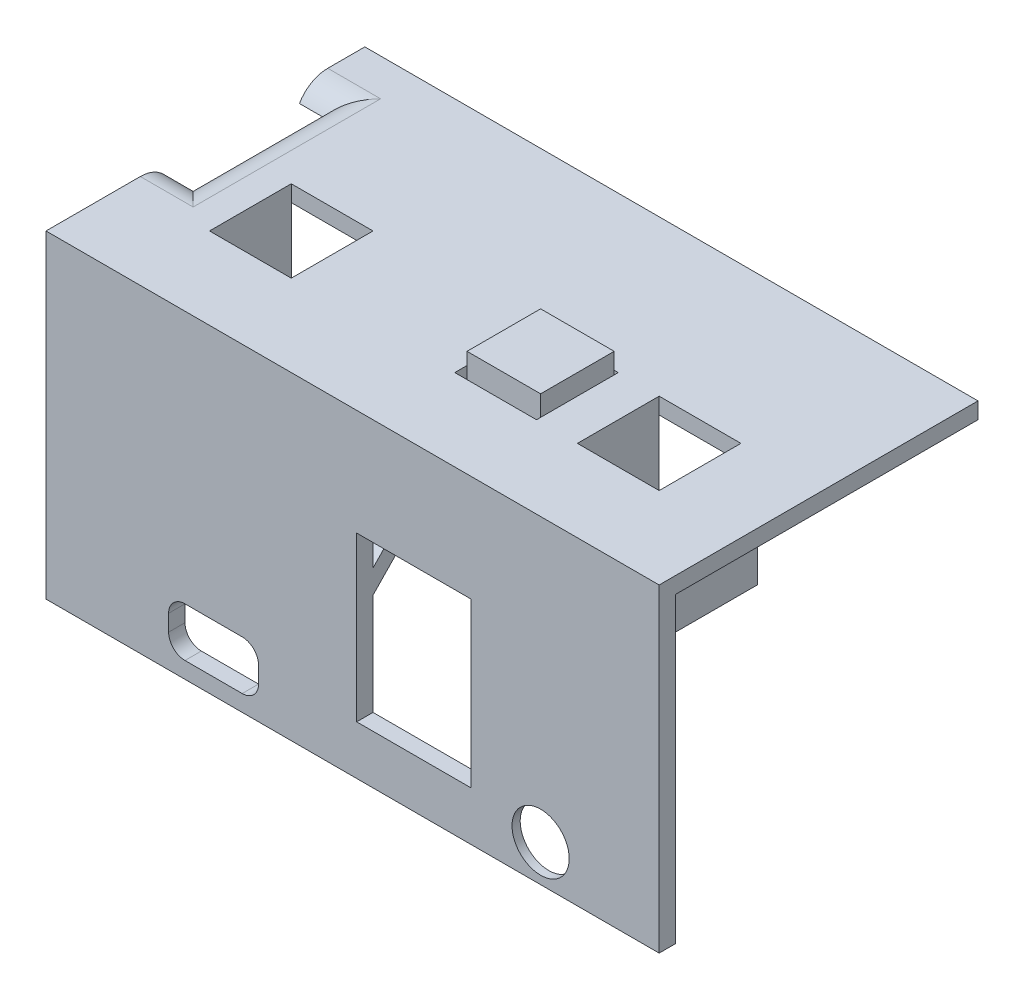
SolidWorks part; units mm, degrees
ref_plane "Front Plane" through (0, 0, 0) normal (0, 0, 1) x (1, 0, 0)
ref_plane "Top Plane" through (0, 0, 0) normal (0, 1, 0) x (1, 0, 0)
ref_plane "Right Plane" through (0, 0, 0) normal (1, 0, 0) x (0, 0, -1)
sketch "Sketch1" plane through (0, 0, 0) normal (0, 0, 1) x (1, 0, 0)
  line L1 (-37.5, 19.5) -> (37.5, 19.5)
  line L2 (-37.5, 19.5) -> (-37.5, -19.5)
  line L3 (-37.5, -19.5) -> (37.5, -19.5)
  line L4 (37.5, 19.5) -> (37.5, -19.5)
  point P4 (37.5, 0)
  point P6 (0, -19.5)
  dimension "D1" = 75
  dimension "D2" = 39
extrude "Boss-Extrude1" add sketch "Sketch1" along normal blind 2
sketch "Sketch2" plane through (0, 0, 0) normal (0, 0, -1) x (-1, 0, 0)
  line L0 (37.5, 19.5) -> (37.5, -19.5) construction
  line L1 (-37.5, 19.5) -> (37.5, 19.5)
  line L2 (-37.5, 19.5) -> (-37.5, 17.5)
  line L3 (-37.5, 17.5) -> (37.5, 17.5)
  line L4 (37.5, 19.5) -> (37.5, 17.5)
  dimension "D1" = 2
extrude "Boss-Extrude2" add sketch "Sketch2" along normal blind 38
sketch "Sketch4" plane through (0, 0, 2) normal (0, 0, 1) x (1, 0, 0)
  line L0 (37.5, -10.5) -> (28.5, -10.5) construction
  line L1 (37.5, -19.5) -> (37.5, 19.5) construction
  line L2 (28.5, -10.5) -> (28.5, -19.5) construction
  line L3 (-37.5, -19.5) -> (37.5, -19.5) construction
  line L4 (23, -19.5) -> (23, -15) construction
  line L5 (-37.5, 19.5) -> (-37.5, -19.5) construction
  line L6 (37.5, 19.5) -> (-37.5, 19.5) construction
  line L7 (-22.5, -11.5) -> (-11.5, -11.5)
  line L8 (-22.5, -11.5) -> (-22.5, -17.5)
  line L9 (-22.5, -17.5) -> (-11.5, -17.5)
  line L10 (-11.5, -11.5) -> (-11.5, -17.5)
  circle A0 centre (23, -15) radius 3.5
  circle A1 centre (23, 4.5) radius 2.25
  dimension "D5" = 7
  dimension "D10" = 4.5
  dimension "D1" = 9
  dimension "D2" = 9
  dimension "D3" = 4.5
  dimension "D4" = 14.5
  dimension "D6" = 15
  dimension "D7" = 49
  dimension "D8" = 2
  dimension "D9" = 6
  dimension "D11" = 15
extrude "Cut-Extrude1" cut sketch "Sketch4" against normal up to surface (2 mm away) up to face at (0, -1, 0)
sketch "Sketch6" plane through (0, 19.5, 0) normal (0, 1, 0) x (1, 0, 0)
  line L0 (37.5, -2) -> (37.5, 38) construction
  line L1 (2.5, 18) -> (12.5, 18)
  line L2 (2.5, 18) -> (2.5, 8)
  line L3 (2.5, 8) -> (12.5, 8)
  line L4 (12.5, 18) -> (12.5, 8)
  line L5 (17.5, 18) -> (27.5, 18)
  line L6 (17.5, 18) -> (17.5, 8)
  line L7 (17.5, 8) -> (27.5, 8)
  line L8 (27.5, 18) -> (27.5, 8)
  line L9 (37.5, -2) -> (-37.5, -2) construction
  line L10 (-37.5, -2) -> (-37.5, 38) construction
  line L11 (-27.5, 18) -> (-17.5, 18)
  line L12 (-27.5, 18) -> (-27.5, 8)
  line L13 (-27.5, 8) -> (-17.5, 8)
  line L14 (-17.5, 18) -> (-17.5, 8)
  dimension "D1" = 10
  dimension "D2" = 10
  dimension "D3" = 5
  dimension "D4" = 10
  dimension "D5" = 10
  dimension "D6" = 10
  dimension "D7" = 10
  dimension "D8" = 10
  dimension "D9" = 10
  dimension "D10" = 10
  dimension "D11" = 10
  dimension "D12" = 10
extrude "Cut-Extrude2" cut sketch "Sketch6" against normal up to surface (2 mm away) up to face at (0, 17.5, -19)
sketch "Sketch7" plane through (0, 17.5, 0) normal (0, -1, 0) x (1, 0, 0)
  line L0 (12.5, -18) -> (12.5, -8) construction
  line L2 (17.5, -8) -> (17.5, -18)
  line L3 (17.5, -18) -> (15.5, -18)
  line L4 (15.5, -8) -> (15.5, -18)
  line L6 (27.5, -8) -> (27.5, -18)
  line L7 (27.5, -18) -> (29.5, -18)
  line L8 (29.5, -8) -> (29.5, -18)
  line L9 (17.5, -8) -> (27.5, -8)
  line L10 (15.5, -8) -> (15.5, -6)
  line L11 (15.5, -6) -> (29.5, -6)
  line L12 (29.5, -8) -> (29.5, -6)
  line L14 (2.5, -8) -> (2.5, -18)
  line L15 (2.5, -18) -> (0.5, -18)
  line L16 (0.5, -8) -> (0.5, -18)
  line L17 (12.5, -18) -> (14.5, -18)
  line L18 (12.5, -18) -> (12.5, -8)
  line L20 (14.5, -18) -> (14.5, -8)
  line L22 (12.5, -8) -> (2.5, -8)
  line L23 (14.5, -8) -> (14.5, -6)
  line L24 (14.5, -6) -> (0.5, -6)
  line L25 (0.5, -8) -> (0.5, -6)
  line L27 (-17.5, -8) -> (-17.5, -18)
  line L28 (-17.5, -18) -> (-15.5, -18)
  line L29 (-15.5, -8) -> (-15.5, -18)
  line L30 (-27.5, -18) -> (-29.5, -18)
  line L31 (-27.5, -18) -> (-27.5, -8)
  line L33 (-29.5, -18) -> (-29.5, -8)
  line L34 (-27.5, -8) -> (-17.5, -8)
  line L35 (-29.5, -8) -> (-29.5, -6)
  line L36 (-29.5, -6) -> (-15.5, -6)
  line L37 (-15.5, -8) -> (-15.5, -6)
  dimension "D1" = 2
  dimension "D2" = 2
  dimension "D3" = 2
  dimension "D4" = 2
  dimension "D5" = 2
  dimension "D6" = 2
  dimension "D7" = 2
  dimension "D8" = 2
  dimension "D9" = 2
extrude "Boss-Extrude3" add sketch "Sketch7" along normal blind 10
sketch "Sketch8" plane through (0, 7.5, 0) normal (0, -1, 0) x (1, 0, 0)
  line L1 (-29.5, -6) -> (-15.5, -6)
  line L2 (-29.5, -6) -> (-29.5, -18)
  line L3 (-29.5, -18) -> (-15.5, -18)
  line L4 (-15.5, -6) -> (-15.5, -18)
  line L5 (0.5, -6) -> (14.5, -6)
  line L6 (0.5, -6) -> (0.5, -18)
  line L7 (0.5, -18) -> (14.5, -18)
  line L8 (14.5, -6) -> (14.5, -18)
  line L9 (15.5, -6) -> (29.5, -6)
  line L10 (15.5, -6) -> (15.5, -18)
  line L11 (15.5, -18) -> (29.5, -18)
  line L12 (29.5, -6) -> (29.5, -18)
extrude "Boss-Extrude4" add sketch "Sketch8" along normal blind 2
sketch "Sketch9" plane through (0, 17.5, 0) normal (0, -1, 0) x (1, 0, 0)
  line L1 (2.5, -18) -> (12.5, -18)
  line L5 (2.5, -8) -> (12.5, -8)
  line L6 (2.5, -8) -> (2.5, -18)
  line L7 (2.5, -18) -> (12.5, -18)
  line L8 (12.5, -8) -> (12.5, -18)
  line L12 (2.5, -18) -> (12.5, -18) construction
  line L13 (0.5, -6) -> (0.5, -18) construction
  line M10 (12.5, -18) -> (2.5, -18)
  dimension "D1" = 10
  dimension "D2" = 10
  dimension "D3" = 0
  dimension "D4" = 2
extrude "Boss-Extrude5" add sketch "Sketch9" against normal blind 4 separate body contours L8 L5 L6 M10
sketch "Sketch10" plane through (0, 17.5, 0) normal (0, -1, 0) x (1, 0, 0)
  line L19 (2.6, -8.1) -> (12.5, -8.1)
  line L21 (2.6, -8.1) -> (12.5, -8.1)
  line L22 (2.6, -8.1) -> (2.6, -18)
  line L23 (2.6, -18) -> (12.5, -18)
  line L24 (12.5, -8.1) -> (12.5, -18)
  line L25 (4.6, -10.1) -> (10.5, -10.1)
  line L26 (4.6, -10.1) -> (4.6, -16)
  line L27 (4.6, -16) -> (10.5, -16)
  line L28 (10.5, -10.1) -> (10.5, -16)
  line M3 (12.5, -18) -> (12.5, -8)
  line M6 (2.5, -18) -> (12.5, -18)
  dimension "D1" = 9.9
  dimension "D2" = 9.9
  dimension "D3" = 2
  dimension "D4" = 2
  dimension "D5" = 2
  dimension "D6" = 2
extrude "Boss-Extrude9" add sketch "Sketch10" along normal blind 2 contours L19 L22 L25 L28 L27 L26 M6 M3
sketch "Sketch11" plane through (0, 0, -18) normal (0, 0, -1) x (-1, 0, 0)
  line L0 (-12.5, 7.5) -> (-12.5, 17.5) construction
  line L1 (-2.6, 15.5) -> (-12.5, 15.5)
  line L2 (-2.6, 15.5) -> (-2.6, 17.35)
  line L3 (-2.6, 17.35) -> (-12.5, 17.35)
  line L4 (-12.5, 15.5) -> (-12.5, 17.35)
  dimension "D1" = 1.85
extrude "Boss-Extrude10" add sketch "Sketch11" along normal blind 4
sketch "Sketch12" plane through (0, 0, 0) normal (0, 0, -1) x (-1, 0, 0)
  circle A0 centre (-23, 4.5) radius 2.25
  circle A1 centre (-23, 4.5) radius 4.25
  dimension "D1" = 2
extrude "Boss-Extrude11" add sketch "Sketch12" along normal blind 2
sketch "Sketch16" plane through (0, 0, 0) normal (0, 0, -1) x (-1, 0, 0)
  line L0 (37.5, -19.5) -> (-23, -19.5) construction
  line L1 (11.5, -11.5) -> (22.5, -11.5)
  line L2 (11.5, -11.5) -> (11.5, -17.5)
  line L3 (11.5, -17.5) -> (22.5, -17.5)
  line L4 (22.5, -11.5) -> (22.5, -17.5)
  line L5 (10, -10) -> (24, -10)
  line L6 (10, -10) -> (10, -19.5)
  line L7 (10, -19.5) -> (24, -19.5)
  line L8 (24, -10) -> (24, -19.5)
  dimension "D1" = 1.5
  dimension "D2" = 1.5
  dimension "D3" = 1.5
extrude "Boss-Extrude13" add sketch "Sketch16" along normal blind 2
sketch "Sketch17" plane through (0, 17.5, 0) normal (0, -1, 0) x (1, 0, 0)
  line L0 (2.5, -8) -> (12.5, -8) construction
  line L1 (2.5, -18) -> (2.6, -18)
  line L2 (2.5, -18) -> (2.5, -8)
  line L3 (2.5, -8) -> (2.6, -8)
  line L4 (2.6, -18) -> (2.6, -8.1)
  line L6 (2.5, -8) -> (12.5, -8)
  line L7 (2.5, -8) -> (2.5, -8.1)
  line L8 (2.6, -8.1) -> (12.5, -8.1)
  line L9 (12.5, -8) -> (12.5, -8.1)
  line M7 (2.6, -18) -> (2.6, -8.1)
  line M8 (2.6, -8.1) -> (12.5, -8.1)
  line M9 (12.5, -8.1) -> (12.5, -8)
  line M10 (12.5, -8) -> (2.5, -8)
  line M11 (2.5, -8) -> (2.5, -18)
  line M12 (2.5, -18) -> (2.6, -18)
extrude "Cut-Extrude3" cut sketch "Sketch17" against normal through all contours L2 M12 M7 M8 M9 M10 M11
fillet "Fillet1" radius 2 4 edges at (-22.5, -17.5, 0) (-22.5, -11.5, 0) (-11.5, -17.5, 0) (-11.5, -11.5, 0)
fillet "Fillet2" radius 2 2 edges at (-24, -10, -1) (-10, -10, -1)
ref_plane "Plane1" through (0, 0, 0) normal (-1, 0, 0) x (0, 0, 1)
sketch "Sketch18" plane through (0, 0, 0) normal (-1, 0, 0) x (0, 0, 1)
  line L0 (-15.1663, 17.5) -> (0, 1.7996)
  line L5 (-17.9471, 17.5) -> (0, -1.079)
  line L6 (-38, 17.5) -> (0, 17.5) construction
  line L7 (0, 17.5) -> (0, -19.5) construction
  line L8 (-17.9471, 17.5) -> (-15.1663, 17.5)
  line L9 (0, -1.079) -> (0, 1.7996)
  dimension "D3" = 2
extrude "Boss-Extrude14" add sketch "Sketch18" along normal blind 2 and the other way blind 2
sketch "Sketch19" plane through (0, 0, 0) normal (0, 0, -1) x (-1, 0, 0)
  line L1 (-14.5, 6.5) -> (-0.5, 6.5)
  line L2 (-14.5, 6.5) -> (-14.5, -13.5)
  line L3 (-14.5, -13.5) -> (-0.5, -13.5)
  line L4 (-0.5, 6.5) -> (-0.5, -13.5)
  line L5 (10, -19.5) -> (-37.5, -19.5) construction
  line L6 (-37.5, -19.5) -> (-37.5, 17.5) construction
  dimension "D1" = 14
  dimension "D2" = 20
  dimension "D3" = 6
  dimension "D4" = 23
extrude "Cut-Extrude4" cut sketch "Sketch19" against normal blind 10 and the other way blind 7
sketch "Sketch22" plane through (0, 0, -38) normal (0, 0, -1) x (-1, 0, 0)
  line L0 (37.5, 19.5) -> (-37.5, 19.5) construction
  line L1 (-29.5, 5.5) -> (-15.5, 5.5)
  line L2 (-29.5, 5.5) -> (-29.5, 19.5)
  line L3 (-29.5, 19.5) -> (-15.5, 19.5)
  line L4 (-15.5, 5.5) -> (-15.5, 19.5)
  line L5 (37.5, 17.5) -> (37.5, -19.5) construction
  line L6 (29.5, 5.5) -> (15.5, 5.5)
  line L7 (29.5, 5.5) -> (29.5, 19.5)
  line L8 (29.5, 19.5) -> (15.5, 19.5)
  line L9 (15.5, 5.5) -> (15.5, 19.5)
  line L10 (-37.5, -19.5) -> (-37.5, 17.5) construction
  dimension "D1" = 14
  dimension "D2" = 14
  dimension "D3" = 8
  dimension "D4" = 8
  dimension "D5" = 14
extrude "Boss-Extrude15" add sketch "Sketch22" against normal blind 3
fillet "Fillet3" radius 7 4 edges at (-29.5, 5.5, -36.5) (-15.5, 5.5, -36.5) (15.5, 5.5, -36.5) (29.5, 5.5, -36.5)
sketch "Sketch23" plane through (0, 0, -38) normal (0, 0, -1) x (-1, 0, 0)
  circle A0 centre (-22.5, 12.5) radius 3.05
  circle A1 centre (22.5, 12.5) radius 3.05
  dimension "D1" = 6.1
  dimension "D2" = 6.1
extrude "Cut-Extrude6" cut sketch "Sketch23" against normal blind 4
sketch "Sketch24" plane through (0, 5.5, 0) normal (0, -1, 0) x (1, 0, 0)
  line L1 (15.5, -6) -> (14.5, -6)
  line L2 (15.5, -6) -> (15.5, -18)
  line L3 (15.5, -18) -> (14.5, -18)
  line L4 (14.5, -6) -> (14.5, -18)
extrude "Boss-Extrude16" add sketch "Sketch24" against normal up to surface (12 mm away) up to face at (0, 17.5, -30.6667)
sketch "Sketch25" plane through (0, 0, -2) normal (0, 0, -1) x (-1, 0, 0)
  line L0 (-31.1594, -19.4878) -> (-14.8406, -19.4878)
  line L1 (10, -19.5) -> (24, -19.5)
  line L2 (10, -19.5) -> (10, -9.8075)
  line L3 (10, -9.8075) -> (24, -9.8075)
  line L4 (24, -19.5) -> (24, -9.8075)
  line L5 (-31.1594, -19.4878) -> (-31.1594, -10.5122)
  line L6 (-14.8406, -19.4878) -> (-14.8406, -10.5122)
  line L7 (-31.1594, -10.5122) -> (-14.8406, -10.5122)
  line L8 (-31.1594, -19.4878) -> (-14.8406, -10.5122) construction
  line L9 (-14.8406, -19.4878) -> (-31.1594, -10.5122) construction
  point P6 (-23, -15)
extrude "Cut-Extrude7" cut sketch "Sketch25" against normal blind 2
sketch "Sketch26" plane through (0, 0, -2) normal (0, 0, -1) x (-1, 0, 0)
  circle A0 centre (-23, 4.5) radius 4.25
extrude "Cut-Extrude8" cut sketch "Sketch26" against normal up to surface (2 mm away) up to face at (0, -1, 0)
sketch "Sketch27" plane through (0, 0, 2) normal (0, 0, 1) x (1, 0, 0)
  circle A0 centre (23, 4.5) radius 2.25
extrude "Boss-Extrude17" add sketch "Sketch27" along a picked direction on the side against the normal up to surface (2 mm away)
sketch "Sketch28" plane through (0, 0, -38) normal (0, 0, -1) x (-1, 0, 0)
  line L1 (-42.4925, 24.9847) -> (43.0335, 24.9847)
  line L2 (-42.4925, 24.9847) -> (-42.4925, -1.8022)
  line L3 (-42.4925, -1.8022) -> (43.0335, -1.8022)
  line L4 (43.0335, 24.9847) -> (43.0335, -1.8022)
extrude "Cut-Extrude9" cut sketch "Sketch28" against normal blind 1
sketch "Sketch29" plane through (0, 0, -35) normal (0, 0, 1) x (1, 0, 0)
  line L1 (15.5, 17.5) -> (29.5, 17.5)
  line L2 (15.5, 17.5) -> (15.5, 12.5)
  line L4 (29.5, 17.5) -> (29.5, 12.5)
  arc A0 (15.5, 12.5) -> (29.5, 12.5) centre (22.5, 12.5) ccw
extrude "Boss-Extrude18" add sketch "Sketch29" along normal blind 1
mirror "Mirror1" about plane through (0, 0, 0) normal (-1, 0, 0) of "Boss-Extrude18"
sketch "Sketch30" plane through (0, 21.5, 0) normal (0, 1, 0) x (1, 0, 0)
  line L0 (2.5, 8) -> (12.5, 8) construction
  line L1 (2.5, 18) -> (3, 18)
  line L2 (2.5, 18) -> (2.5, 8)
  line L4 (3, 18) -> (3, 8.5)
  line L6 (12.5, 8) -> (2.5, 8)
  line L7 (12.5, 8) -> (12.5, 8.5)
  line L8 (12.5, 8.5) -> (3, 8.5)
  dimension "D1" = 0.5
  dimension "D2" = 0.5
extrude "Cut-Extrude10" cut sketch "Sketch30" against normal blind 10
sketch "Sketch31" plane through (0, 0, 0) normal (0, 0, -1) x (-1, 0, 0)
  line L0 (37.5, -19.5) -> (-37.5, -19.5) construction
  line L1 (-32, -10.5) -> (-17, -10.5)
  line L2 (-32, -10.5) -> (-32, -19.5)
  line L3 (-32, -19.5) -> (-17, -19.5)
  line L4 (-17, -10.5) -> (-17, -19.5)
  circle A0 centre (-23, -15) radius 3.5 construction
  circle A1 centre (-23, -15) radius 3.5
  dimension "D3" = 6
  dimension "D4" = 7
  dimension "D1" = 15
  dimension "D2" = 9
extrude "Cut-Extrude11" cut sketch "Sketch31" against normal blind 1
sketch "Sketch32" plane through (0, 17.5, 0) normal (0, -1, 0) x (1, 0, 0)
  line L0 (-37.5, -37) -> (37.5, -37) construction
  line L1 (-10, -24) -> (10, -24)
  line L2 (-10, -24) -> (-10, -32)
  line L3 (-10, -32) -> (10, -32)
  line L4 (10, -24) -> (10, -32)
  point P8 (0, -37)
  point P9 (0, -32)
  dimension "D1" = 20
  dimension "D2" = 8
  dimension "D3" = 5
extrude "Cut-Extrude12" cut sketch "Sketch32" against normal blind 1
sketch "Sketch33" plane through (0, 6.5, 0) normal (0, -1, 0) x (1, 0, 0)
  line L0 (0.5, -7) -> (0.5, -4.5405) construction
  line L1 (14.5, -7) -> (0.5, -7)
  line L2 (14.5, -7) -> (14.5, -5.7703)
  line L3 (14.5, -5.7703) -> (0.5, -5.7703)
  line L4 (0.5, -7) -> (0.5, -5.7703)
sketch "Sketch34" plane through (0, 5.5, 0) normal (0, -1, 0) x (1, 0, 0)
  line L0 (0.5, -7) -> (0.5, -4.5405) construction
  line L1 (14.5, -7) -> (0.5, -7)
  line L2 (14.5, -7) -> (14.5, -6)
  line L3 (14.5, -6) -> (0.5, -6)
  line L4 (0.5, -7) -> (0.5, -6)
  line L5 (29.5, -6) -> (0.5, -6) construction
extrude "Boss-Extrude19" add sketch "Sketch34" along normal up to surface (1 mm away)
sketch "Sketch35" plane through (0, 19.5, 0) normal (0, 1, 0) x (1, 0, 0)
  line L0 (-37.5, -2) -> (-37.5, 37) construction
  line L1 (-37.5, 29) -> (-34.5, 29)
  line L2 (-37.5, 29) -> (-37.5, 13)
  line L3 (-37.5, 13) -> (-34.5, 13)
  line L4 (-34.5, 29) -> (-34.5, 13)
  line L5 (-37.5, 37) -> (37.5, 37) construction
  dimension "D1" = 16
  dimension "D2" = 3
  dimension "D3" = 8
extrude "Cut-Extrude13" cut sketch "Sketch35" against normal through all
fillet "Fillet4" radius 4 3 edges at (-36, 19.5, -13) (-36, 19.5, -29) (-34.5, 19.5, -21)
sketch "Sketch36" plane through (0, 15.5, 0) normal (0, -1, 0) x (1, 0, 0)
  line L0 (12.5, -22) -> (2.6, -22) construction
  line L1 (3, -18) -> (2.6, -18)
  line L2 (3, -18) -> (3, -22)
  line L3 (3, -22) -> (2.6, -22)
  line L4 (2.6, -18) -> (2.6, -22)
  line L5 (2.6, -18) -> (2.6, -22) construction
extrude "Cut-Extrude14" cut sketch "Sketch36" against normal blind 10
sketch "Sketch38" plane through (0, 15.5, 0) normal (0, -1, 0) x (1, 0, 0)
  line L0 (12.5, -22) -> (12.5, -8.5) construction
  line L1 (3, -8.5) -> (12.5, -8.5)
  line L2 (3, -8.5) -> (3, -16)
  line L3 (3, -16) -> (12.5, -16)
  line L4 (12.5, -8.5) -> (12.5, -16)
extrude "Cut-Extrude15" cut sketch "Sketch38" against normal up to surface (2 mm away) up to face at (7.55, 17.5, -13.05)
sketch "Sketch39" plane through (0, 21.5, 0) normal (0, 1, 0) x (1, 0, 0)
  line L18 (12.5, 8.5) -> (3, 8.5)
  line L19 (3, 8.5) -> (3, 9)
  line L20 (3, 8.5) -> (3, 18) construction
  line L21 (3, 9) -> (12, 9)
  line L22 (12, 9) -> (12, 22)
  line L23 (3, 22) -> (12.5, 22) construction
  line L24 (12, 22) -> (12.5, 22)
  line L25 (12.5, 22) -> (12.5, 8.5)
  dimension "D1" = 0.5
  dimension "D2" = 0.5
extrude "Cut-Extrude16" cut sketch "Sketch39" against normal blind 10
